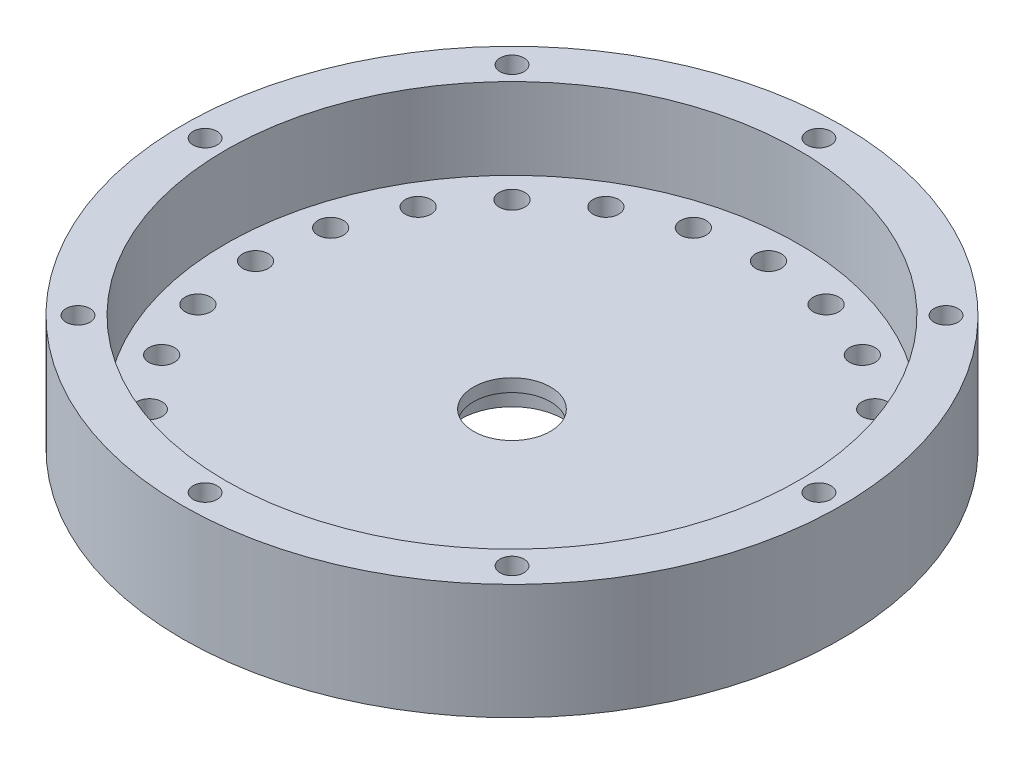
SolidWorks part; units mm, degrees
ref_plane "Front Plane" through (0, 0, 0) normal (0, 0, 1) x (1, 0, 0)
ref_plane "Top Plane" through (0, 0, 0) normal (0, 1, 0) x (1, 0, 0)
ref_plane "Right Plane" through (0, 0, 0) normal (1, 0, 0) x (0, 0, -1)
sketch "Sketch1" plane through (0, 0, 0) normal (0, 1, 0) x (1, 0, 0)
  circle A0 centre (0, 0) radius 77.1
  dimension "D1" = 154.2
extrude "Boss-Extrude1" add sketch "Sketch1" along normal blind 27
sketch "Sketch2" plane through (0, 27, 0) normal (0, 1, 0) x (1, 0, 0)
  circle A0 centre (0, 0) radius 67
  dimension "D1" = 134
extrude "Cut-Extrude1" cut sketch "Sketch2" against normal blind 19
sketch "Sketch3" plane through (0, 8, 0) normal (0, 1, 0) x (1, 0, 0)
  circle A1 centre (60, 0) radius 3
  circle A2 centre (57.9555, -15.5291) radius 3
  circle A3 centre (51.9615, -30) radius 3
  circle A4 centre (42.4264, -42.4264) radius 3
  circle A5 centre (30, -51.9615) radius 3
  circle A6 centre (15.5291, -57.9555) radius 3
  circle A7 centre (0, -60) radius 3
  circle A8 centre (-15.5291, -57.9555) radius 3
  circle A9 centre (-30, -51.9615) radius 3
  circle A10 centre (-42.4264, -42.4264) radius 3
  circle A11 centre (-51.9615, -30) radius 3
  circle A12 centre (-57.9555, -15.5291) radius 3
  circle A13 centre (-60, 0) radius 3
  circle A14 centre (-57.9555, 15.5291) radius 3
  circle A15 centre (-51.9615, 30) radius 3
  circle A16 centre (-42.4264, 42.4264) radius 3
  circle A17 centre (-30, 51.9615) radius 3
  circle A18 centre (-15.5291, 57.9555) radius 3
  circle A19 centre (0, 60) radius 3
  circle A20 centre (15.5291, 57.9555) radius 3
  circle A21 centre (30, 51.9615) radius 3
  circle A22 centre (42.4264, 42.4264) radius 3
  circle A27 centre (51.9615, 30) radius 3
  circle A28 centre (57.9555, 15.5291) radius 3
  point P13 (0, 0)
  dimension "D2" = 60
  dimension "D3" = 24
extrude "Cut-Extrude2" cut sketch "Sketch3" against normal blind 5
sketch "Sketch4" plane through (0, 0, 0) normal (0, -1, 0) x (1, 0, 0)
  circle A0 centre (0, 0) radius 12
  dimension "D1" = 24
extrude "Cut-Extrude3" cut sketch "Sketch4" against normal blind 5
sketch "Sketch5" plane through (0, 8, 0) normal (0, 1, 0) x (1, 0, 0)
  circle A0 centre (0, 0) radius 9
  dimension "D1" = 18
extrude "Cut-Extrude4" cut sketch "Sketch5" against normal blind 5
sketch "Sketch6" plane through (0, 27, 0) normal (0, 1, 0) x (1, 0, 0)
  line L0 (0, 71.8) -> (0, 0) construction
  circle A0 centre (0, 71.8) radius 2.8
  circle A3 centre (50.7703, 50.7703) radius 2.8
  circle A4 centre (71.8, 0) radius 2.8
  circle A5 centre (50.7703, -50.7703) radius 2.8
  circle A6 centre (0, -71.8) radius 2.8
  circle A7 centre (-50.7703, -50.7703) radius 2.8
  circle A8 centre (-71.8, 0) radius 2.8
  circle A9 centre (-50.7703, 50.7703) radius 2.8
  point P19 (0, 0)
  dimension "D3" = 71.8
  dimension "D2" = 8
extrude "Cut-Extrude5" cut sketch "Sketch6" against normal blind 8
equation "\"N_pin\"= 24"
equation "\"R_pin\"= 60"
equation "\"d_pin\"= 13"
equation "\"e\"= 1.5"
equation "\"t_disk\"= 5"
equation "\"N_outpin\"= 8"
equation "\"R_outpin\"= 34"
equation "\"d_outpin\"= 13"
equation "\"N_lobes\"= \"N_pin\" - 1"
equation "\"d_outhole\"= \"d_outpin\" + 2 * \"e\""
equation "\"ratio\"= \"N_lobes\""
equation "\"d_center\"= 24"
equation "\"a_hole1\"= 0 / \"N_lobes\""
equation "\"a_hole2\"= 360 / \"N_disk\" / \"N_lobes\""
equation "\"a_hole3\"= 720 / \"N_disk\" / \"N_lobes\""
equation "\"N_disk\"= 3"
equation "\"t_gap\"= 1"
equation "\"L_stack\"= \"N_disk\" * \"t_disk\" + (\"N_disk\" - 1) * \"t_gap\""
equation "\"d_pinshaft\"= 6"
equation "\"d_ecc\"= 15"
equation "\"d_outbrg\"= 47"
equation "\"w_outbrg\"= 7"
equation "\"d_outshaft\"= 35"
equation "\"w_brg\"= 5"
equation "\"c_run\"= 0.5"
equation "\"c_ax\"= \"t_gap\""
equation "\"D_pocket\"= 2 * \"R_pin\" + \"d_pin\" + 2 * \"c_run\""
equation "\"h_pocket\"= \"L_stack\" + 2 * \"c_ax\""
equation "\"t_floor\"= 8"
equation "\"d_insert\"= 5.6"
equation "\"N_bolt\"= 8"
equation "\"R_bolt\"= \"D_pocket\" / 2 + 2 + \"d_insert\" / 2"
equation "\"D_housing\"= 2 * (\"R_bolt\" + \"d_insert\" / 2 + 2.5)"
equation "\"D1@Sketch1\"=\"D_housing\""
equation "\"D1@Boss-Extrude1\"=\"t_floor\"+\"h_pocket\""
equation "\"D1@Sketch2\"=\"D_pocket\""
equation "\"D1@Cut-Extrude1\"=\"h_pocket\""
equation "\"D1@Sketch3\"=\"d_pinshaft\""
equation "\"D2@Sketch3\"=\"R_pin\""
equation "\"D1@Cut-Extrude2\"=\"t_floor\"-3"
equation "\"D3@Sketch3\"=\"N_pin\""
equation "\"D1@Sketch4\"=\"d_center\""
equation "\"D1@Cut-Extrude3\"=\"w_brg\""
equation "\"D1@Sketch5\"=\"d_ecc\"+3"
equation "\"D1@Sketch6\"=\"d_insert\""
equation "\"D2@Sketch6\"=\"N_bolt\""
equation "\"D3@Sketch6\"=\"R_bolt\""
